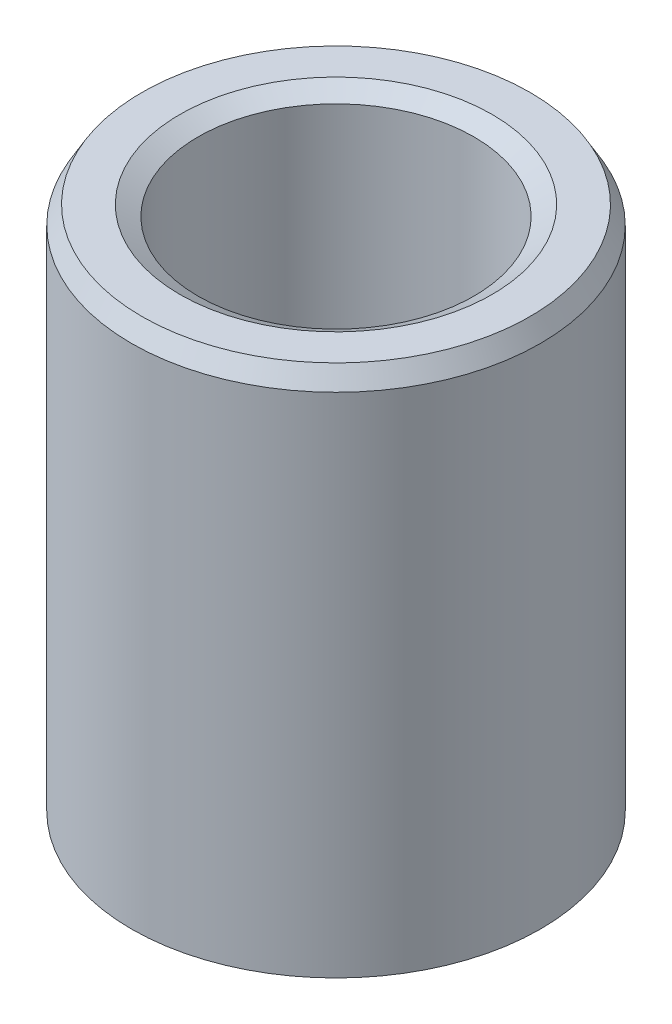
SolidWorks part; units mm, degrees
ref_plane "Front Plane" through (0, 0, 0) normal (0, 0, 1) x (1, 0, 0)
ref_plane "Top Plane" through (0, 0, 0) normal (0, 1, 0) x (1, 0, 0)
ref_plane "Right Plane" through (0, 0, 0) normal (1, 0, 0) x (0, 0, -1)
sketch "Sketch1" plane through (0, 0, 0) normal (0, 1, 0) x (1, 0, 0)
  circle A0 centre (0, 0) radius 17.5
  dimension "SLEEVE_OD" = 35
extrude "Boss-Extrude1" add sketch "Sketch1" along normal blind 45.8369
sketch "Sketch2" plane through (0, 0, 0) normal (0, 1, 0) x (1, 0, 0)
  circle A0 centre (0, 0) radius 11.8063
  dimension "BORE_D" = 23.6126
extrude "Cut-Extrude1" cut sketch "Sketch2" along normal through all
chamfer "Chamfer1" distance 1.5458 angle 30 4 edges at (0, 45.8369, 11.8063) (0, 0, 11.8063) (0, 0, 17.5) (0, 45.8369, 17.5) first distance on face at (0, 45.8369, 11.8063) first distance on face at (0, 0, 11.8063) first distance on face at (0, 45.8369, 17.5)
